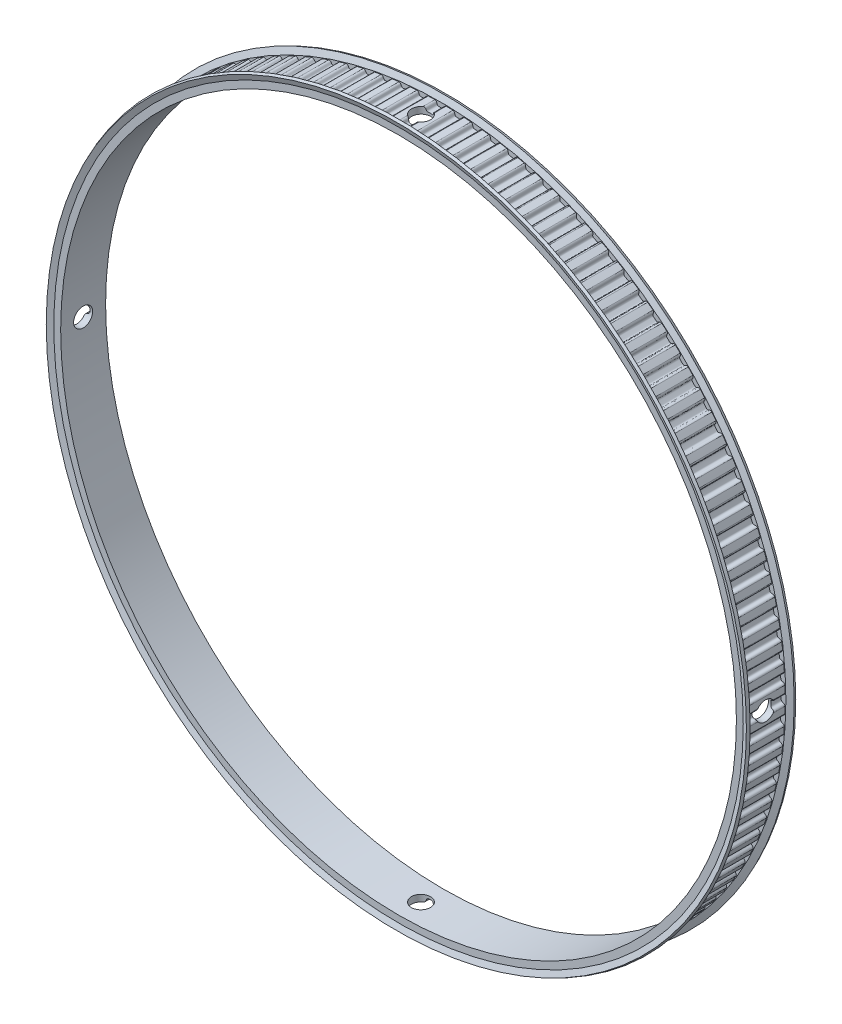
SolidWorks part; units mm, degrees
note: '?' marks a value the reader was unsure of.
ref_plane "前视基准面" through (0, 0, 0) normal (0, 0, 1) x (1, 0, 0)
ref_plane "上视基准面" through (0, 0, 0) normal (0, 1, 0) x (1, 0, 0)
ref_plane "右视基准面" through (0, 0, 0) normal (1, 0, 0) x (0, 0, -1)
other "Configuration Table"
ref_axis "基准轴1" through (0, 0, 55) along (0, 0, -1)?
sketch "SketchRevolveGearBelt01" plane through (0, 0, 0) normal (1, 0, 0) x (0, 0, -1)
  line L0 (0, 0) -> (1, 0) construction
  line L1 (12.7, 0) -> (12.7, 177.6469)
  line L2 (12.7, 177.6469) -> (11.8377, 177.6469)
  line L3 (11.8377, 177.6469) -> (11.8377, 181.612)
  line L4 (11.8377, 181.612) -> (13.003, 184.4253)
  line L5 (13.003, 184.4253) -> (11.5997, 185.0065)
  line L6 (11.5997, 185.0065) -> (10.3187, 181.9141)
  line L7 (10.3187, 181.9141) -> (10.3187, 181.5204)
  line L8 (10.3187, 181.5204) -> (-10.3187, 181.5204)
  line L9 (-10.3187, 181.5204) -> (-10.3187, 181.9141)
  line L10 (-10.3187, 181.9141) -> (-11.5997, 185.0065)
  line L11 (-11.5997, 185.0065) -> (-13.003, 184.4253)
  line L12 (-13.003, 184.4253) -> (-11.8377, 181.612)
  line L13 (-11.8377, 181.612) -> (-11.8377, 177.6469)
  line L14 (-11.8377, 177.6469) -> (-12.7, 177.6469)
  line L15 (-12.7, 177.6469) -> (-12.7, 0)
  line L16 (-12.7, 0) -> (12.7, 0)
  dimension "GearBeltFlange1OutsideLength" = 3.9651
  dimension "GearBeltFlange1X" = 1.1653
  dimension "GearBeltFlange1Y" = 2.8133
  dimension "GearBeltFlangeThickness" = 1.5189
  dimension "GearBeltFlangeInside" = 0.3937
  dimension "GearBeltOutsideDiameter" = 181.5204
  dimension "GearBeltFlange2X" = 1.1653
revolve "L_节距_0_375in, 0.750in Belt Width" add sketch "SketchRevolveGearBelt01" angle 360 about L0
sketch "SketchToothGearBelt01" plane through (0, 0, 0) normal (0, 0, 1) x (1, 0, 0)
  arc A0 (181.5057, 3.1561) -> (181.5057, -3.1561) centre (0, 0) cw
  spline S0 degree 3 poles (181.5057, -3.1561) (181.5087, -2.9943) (181.4614, -2.7509) (181.3049, -2.4657) (181.1459, -2.2807) (180.9524, -2.132) (180.7929, -2.057) (180.6913, -2.0216) (180.6534, -2.008) (180.6156, -1.9947) (180.5778, -1.9813) (180.54, -1.968) (180.5024, -1.9547) (180.4648, -1.9415) (180.4272, -1.9284) (180.3898, -1.9153) (180.3524, -1.9023) (180.3151, -1.8893) (180.2778, -1.8764) (180.2406, -1.8635) (180.2035, -1.8506) (180.1664, -1.8379) (180.1294, -1.8251) (180.0699, -1.8046) (180.0145, -1.7863) (179.9642, -1.7658) (179.9394, -1.755) (179.9129, -1.7426) (179.8845, -1.7282) (179.8538, -1.7115) (179.8207, -1.6917) (179.7847, -1.6681) (179.7455, -1.6396) (179.7032, -1.6051) (179.6576, -1.5629) (179.6092, -1.5111) (179.5593, -1.4476) (179.5099, -1.3706) (179.4643, -1.2788) (179.427, -1.1725) (179.4018, -1.0551) (179.3856, -0.6622) (179.4118, 0) (179.3856, 0.6622) (179.4018, 1.0551) (179.427, 1.1725) (179.4643, 1.2788) (179.5099, 1.3706) (179.5593, 1.4476) (179.6092, 1.5111) (179.6576, 1.5629) (179.7032, 1.6051) (179.7455, 1.6396) (179.7847, 1.6681) (179.8207, 1.6917) (179.8538, 1.7115) (179.8845, 1.7282) (179.9129, 1.7426) (179.9394, 1.755) (179.9642, 1.7658) (180.0145, 1.7863) (180.0699, 1.8046) (180.1294, 1.8251) (180.1664, 1.8379) (180.2035, 1.8506) (180.2406, 1.8635) (180.2778, 1.8764) (180.3151, 1.8893) (180.3524, 1.9023) (180.3898, 1.9153) (180.4272, 1.9284) (180.4648, 1.9415) (180.5024, 1.9547) (180.54, 1.968) (180.5778, 1.9813) (180.6156, 1.9947) (180.6534, 2.008) (180.6913, 2.0216) (180.7929, 2.057) (180.9524, 2.132) (181.1459, 2.2807) (181.3049, 2.4657) (181.4614, 2.7509) (181.5087, 2.9943) (181.5057, 3.1561) knots 0 0 0 0 0.056779 0.085168 0.113557 0.141946 0.170336 0.175062 0.17978 0.184487 0.189185 0.193874 0.198554 0.203223 0.207884 0.212535 0.217176 0.221808 0.22643 0.231043 0.235647 0.240241 0.244825 0.2494 0.262381 0.26533 0.26849 0.271901 0.275612 0.27968 0.284177 0.289188 0.294813 0.301171 0.308401 0.316647 0.326058 0.336748 0.348762 0.362018 0.376261 0.390807 0.5 0.609193 0.623739 0.637982 0.651238 0.663252 0.673942 0.683353 0.691599 0.698829 0.705187 0.710812 0.715823 0.72032 0.724388 0.728099 0.73151 0.73467 0.737619 0.7506 0.755175 0.759759 0.764353 0.768957 0.77357 0.778192 0.782824 0.787465 0.792116 0.796777 0.801446 0.806126 0.810815 0.815513 0.82022 0.824938 0.829664 0.858054 0.886443 0.914832 0.943221 1 1 1 1
extrude "ToothExtrudeCutGearBelt01" cut sketch "SketchToothGearBelt01" against normal blind 10.3187 and the other way blind 10.3187
pattern_circular "Tooth Pattern, 120" count 120 every 3 about axis through (0, 0, 55) along (0, 0, -1) of "ToothExtrudeCutGearBelt01"
sketch "BoreRevolveSketch" plane through (0, 0, 0) normal (1, 0, 0) x (0, 0, -1)
  line L0 (0, 0) -> (1, 0) construction
  line L1 (-12.7, 0) -> (12.7, 0)
  line L2 (12.7, 0) -> (12.7, 5)
  line L3 (12.7, 5) -> (-12.7, 5)
  line L4 (-12.7, 5) -> (-12.7, 0)
  dimension "TaperSide1" = 5
  dimension "TaperSide2" = 5
revolve "BoreRevolveCut" cut sketch "BoreRevolveSketch" angle 360 about L0
sketch "AuxiliarySketchGearBelt01" plane through (0, 0, 0) normal (0, 0, 1) x (1, 0, 0)
  circle A0 centre (0, 0) radius 181.9141 construction
  dimension "PitchDiameter" = 363.8282
ref_plane "基准面1" through (0, 0, 22.7) normal (0, 0, 1) x (1, 0, 0)
sketch "草图6" plane through (0, 0, 22.7) normal (0, 0, 1) x (1, 0, 0)
  circle A0 centre (0, 0) radius 178
extrude "切除-拉伸2" cut sketch "草图6" against normal through all
sketch "草图7" plane through (0, 0, 0) normal (0, 1, 0) x (1, 0, 0)
  circle A0 centre (0, 0) radius 5
extrude "切除-拉伸3" cut sketch "草图7" against normal through all both and the other way through all
sketch "草图8" plane through (0, 0, 0) normal (1, 0, 0) x (0, 0, -1)
  circle A0 centre (0, 0) radius 5
extrude "切除-拉伸4" cut sketch "草图8" against normal through all both and the other way through all
